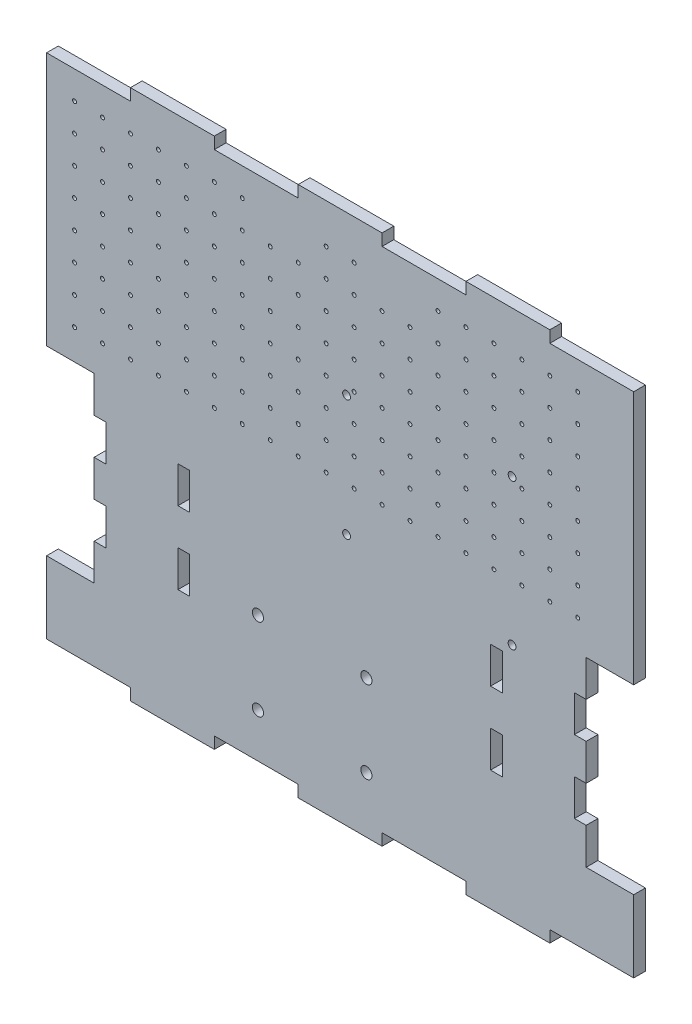
SolidWorks part; units mm, degrees
ref_plane "Front Plane" through (0, 0, 0) normal (0, 0, 1) x (1, 0, 0)
ref_plane "Top Plane" through (0, 0, 0) normal (0, 1, 0) x (1, 0, 0)
ref_plane "Right Plane" through (0, 0, 0) normal (1, 0, 0) x (0, 0, -1)
sketch "Sketch1" plane through (0, 0, 0) normal (0, 0, 1) x (1, 0, 0)
  line L1 (-133.35, 120.65) -> (133.35, 120.65)
  line L2 (-133.35, 120.65) -> (-133.35, -120.65)
  line L3 (-133.35, -120.65) -> (133.35, -120.65)
  line L4 (133.35, 120.65) -> (133.35, -120.65)
  line L5 (-133.35, 120.65) -> (133.35, -120.65) construction
  line L6 (-133.35, -120.65) -> (133.35, 120.65) construction
  point P0 (0, 0)
  dimension "D1" = 241.3
  dimension "D2" = 266.7
extrude "Boss-Extrude1" add sketch "Sketch1" along normal blind 5.334
sketch "Sketch2" plane through (0, 0, 0) normal (0, 0, -1) x (-1, 0, 0)
  line L0 (133.35, 120.65) -> (133.35, -120.65) construction
  line L1 (133.35, 0) -> (111.76, 0)
  line L2 (133.35, 0) -> (133.35, -82.55)
  line L3 (133.35, -82.55) -> (111.76, -82.55)
  line L4 (111.76, 0) -> (111.76, -82.55)
  line L5 (-133.35, -120.65) -> (-133.35, 120.65) construction
  line L6 (-133.35, 0) -> (-111.76, 0)
  line L7 (-133.35, 0) -> (-133.35, -82.55)
  line L8 (-133.35, -82.55) -> (-111.76, -82.55)
  line L9 (-111.76, 0) -> (-111.76, -82.55)
  line L10 (133.35, -120.65) -> (-133.35, -120.65) construction
  dimension "D1" = 82.55
  dimension "D2" = 82.55
  dimension "D3" = 38.1
  dimension "D4" = 38.1
  dimension "D5" = 21.59
  dimension "D6" = 21.59
extrude "Cut-Extrude1" cut sketch "Sketch2" against normal through all
sketch "Sketch9" plane through (0, 0, 5.334) normal (0, 0, 1) x (1, 0, 0)
  line L0 (-111.76, 0) -> (-111.76, -82.55) construction
  line L1 (-111.76, -16.51) -> (-106.426, -16.51)
  line L2 (-111.76, -16.51) -> (-111.76, -33.02)
  line L3 (-111.76, -33.02) -> (-106.426, -33.02)
  line L4 (-106.426, -16.51) -> (-106.426, -33.02)
  line L5 (-111.76, 0) -> (-106.426, 0) construction
  line L6 (-111.76, -49.53) -> (-106.426, -49.53)
  line L7 (-111.76, -49.53) -> (-111.76, -66.04)
  line L8 (-111.76, -66.04) -> (-106.426, -66.04)
  line L9 (-106.426, -49.53) -> (-106.426, -66.04)
  line L10 (-106.426, 0) -> (-106.426, -16.51) construction
  line L11 (-106.426, -33.02) -> (-106.426, -49.53) construction
  line L12 (-111.76, -82.55) -> (-106.426, -82.55) construction
  line L13 (-106.426, -82.55) -> (-106.426, -66.04) construction
  line L14 (0, -120.65) -> (0, 120.65) construction
  line L15 (-133.35, -120.65) -> (133.35, -120.65) construction
  line L16 (133.35, 120.65) -> (-133.35, 120.65) construction
  line L17 (106.426, -82.55) -> (106.426, -66.04) construction
  line L18 (111.76, -82.55) -> (106.426, -82.55) construction
  line L19 (106.426, -33.02) -> (106.426, -49.53) construction
  line L20 (106.426, 0) -> (106.426, -16.51) construction
  line L21 (111.76, 0) -> (106.426, 0) construction
  line L22 (106.426, -49.53) -> (106.426, -66.04)
  line L23 (111.76, -66.04) -> (106.426, -66.04)
  line L24 (111.76, -49.53) -> (111.76, -66.04)
  line L25 (111.76, -49.53) -> (106.426, -49.53)
  line L26 (106.426, -16.51) -> (106.426, -33.02)
  line L27 (111.76, -33.02) -> (106.426, -33.02)
  line L28 (111.76, -16.51) -> (111.76, -33.02)
  line L29 (111.76, -16.51) -> (106.426, -16.51)
  dimension "D1" = 5.334
extrude "Cut-Extrude2" cut sketch "Sketch9" against normal through all
sketch "Sketch10" plane through (0, 0, 5.334) normal (0, 0, 1) x (1, 0, 0)
  line L2 (-133.35, -120.65) -> (133.35, -120.65) construction
  line L3 (-133.35, -82.55) -> (-133.35, -120.65) construction
  circle A0 centre (-37.338, -95.25) radius 2.54
  circle A1 centre (11.938, -95.25) radius 2.54
  circle A2 centre (11.938, -57.912) radius 2.54
  circle A3 centre (-37.338, -57.912) radius 2.54
  dimension "D1" = 96.012
  dimension "D2" = 49.276
  dimension "D3" = 25.4
  dimension "D4" = 2
  dimension "D5" = 2
extrude "Cut-Extrude3" cut sketch "Sketch10" against normal through all
sketch "Sketch23" plane through (0, 0, 5.334) normal (0, 0, 1) x (1, 0, 0)
  line L0 (-106.426, -24.765) -> (-61.976, -24.765) construction
  line L1 (-106.426, -33.02) -> (-106.426, -16.51) construction
  line L2 (-106.426, -16.51) -> (-68.326, -16.51) construction
  line L3 (-106.426, -33.02) -> (-68.326, -33.02) construction
  line L4 (-111.76, -41.275) -> (111.76, -41.275) construction
  line L5 (-111.76, -33.02) -> (-111.76, -49.53) construction
  line L6 (111.76, -49.53) -> (111.76, -33.02) construction
  line L7 (-106.426, -49.53) -> (-68.326, -49.53) construction
  line L8 (-106.426, -57.785) -> (-61.976, -57.785) construction
  line L9 (-106.426, -66.04) -> (-68.326, -66.04) construction
  line L10 (0, -120.65) -> (0, 120.65) construction
  line L11 (-133.35, -120.65) -> (133.35, -120.65) construction
  line L12 (133.35, 120.65) -> (-133.35, 120.65) construction
  line L13 (106.426, -66.04) -> (68.326, -66.04) construction
  line L14 (106.426, -49.53) -> (68.326, -49.53) construction
  line L15 (106.426, -33.02) -> (68.326, -33.02) construction
  line L16 (106.426, -16.51) -> (68.326, -16.51) construction
  line L17 (-68.326, -66.04) -> (-73.66, -66.04)
  line L18 (68.326, -16.51) -> (73.66, -16.51)
  line L19 (68.326, -16.51) -> (68.326, -33.02)
  line L20 (68.326, -33.02) -> (73.66, -33.02)
  line L21 (73.66, -16.51) -> (73.66, -33.02)
  line L22 (68.326, -49.53) -> (73.66, -49.53)
  line L23 (68.326, -49.53) -> (68.326, -66.04)
  line L24 (68.326, -66.04) -> (73.66, -66.04)
  line L25 (73.66, -49.53) -> (73.66, -66.04)
  line L26 (-73.66, -49.53) -> (-73.66, -66.04)
  line L27 (-68.326, -49.53) -> (-68.326, -66.04)
  line L28 (-68.326, -49.53) -> (-73.66, -49.53)
  line L29 (-68.326, -33.02) -> (-73.66, -33.02)
  line L30 (-73.66, -16.51) -> (-73.66, -33.02)
  line L31 (-68.326, -16.51) -> (-73.66, -16.51)
  line L32 (-68.326, -16.51) -> (-68.326, -33.02)
  line L33 (106.426, -16.51) -> (106.426, -33.02) construction
  dimension "D1" = 5.334
  dimension "D2" = 5.334
  dimension "D3" = 32.766
  dimension "D4" = 32.766
extrude "Cut-Extrude8" cut sketch "Sketch23" against normal through all
sketch "Sketch28" plane through (0, 0, 0) normal (0, 0, -1) x (-1, 0, 0)
  line L0 (133.35, -120.65) -> (-133.35, -120.65) construction
  line L1 (-133.35, -120.65) -> (-95.25, -120.65)
  line L2 (-133.35, -120.65) -> (-133.35, -115.316)
  line L3 (-133.35, -115.316) -> (-95.25, -115.316)
  line L4 (-95.25, -120.65) -> (-95.25, -115.316)
  line L5 (-57.15, -120.65) -> (-19.05, -120.65)
  line L6 (-57.15, -120.65) -> (-57.15, -115.316)
  line L7 (-57.15, -115.316) -> (-19.05, -115.316)
  line L8 (-19.05, -120.65) -> (-19.05, -115.316)
  line L9 (133.35, -82.55) -> (133.35, -120.65) construction
  line L10 (19.05, -120.65) -> (57.15, -120.65)
  line L11 (19.05, -120.65) -> (19.05, -115.316)
  line L12 (19.05, -115.316) -> (57.15, -115.316)
  line L13 (57.15, -120.65) -> (57.15, -115.316)
  line L14 (95.25, -120.65) -> (133.35, -120.65)
  line L16 (95.25, -115.316) -> (133.35, -115.316)
  line L17 (133.35, -120.65) -> (133.35, -115.316)
  line L18 (-95.25, -115.316) -> (-57.15, -115.316) construction
  line L19 (-19.05, -115.316) -> (19.05, -115.316) construction
  line L20 (95.25, -115.316) -> (57.15, -115.316) construction
  line L21 (133.35, 120.65) -> (133.35, -115.316) construction
  line L22 (133.35, -115.316) -> (133.5431, -115.1744) construction
  line L41 (95.25, -120.65) -> (95.25, -115.316)
  dimension "D1" = 5.334
extrude "Cut-Extrude13" cut sketch "Sketch28" against normal through all
sketch "Sketch29" plane through (0, 0, 0) normal (0, 0, -1) x (-1, 0, 0)
  line L0 (-133.35, 120.65) -> (133.35, 120.65) construction
  line L1 (-133.35, 120.65) -> (-95.25, 120.65)
  line L2 (-133.35, 120.65) -> (-133.35, 115.316)
  line L3 (-133.35, 115.316) -> (-95.25, 115.316)
  line L4 (-95.25, 120.65) -> (-95.25, 115.316)
  line L5 (-57.15, 120.65) -> (-19.05, 120.65)
  line L6 (-57.15, 120.65) -> (-57.15, 115.316)
  line L7 (-57.15, 115.316) -> (-19.05, 115.316)
  line L8 (-19.05, 120.65) -> (-19.05, 115.316)
  line L9 (133.35, 120.65) -> (133.35, 0) construction
  line L10 (19.05, 120.65) -> (57.15, 120.65)
  line L11 (19.05, 120.65) -> (19.05, 115.316)
  line L12 (19.05, 115.316) -> (57.15, 115.316)
  line L13 (57.15, 120.65) -> (57.15, 115.316)
  line L14 (95.25, 120.65) -> (133.35, 120.65)
  line L15 (95.25, 120.65) -> (95.25, 115.316)
  line L16 (95.25, 115.316) -> (133.35, 115.316)
  line L17 (133.35, 120.65) -> (133.35, 115.316)
  line L18 (-95.25, 115.316) -> (-57.15, 115.316) construction
  line L19 (19.05, 115.316) -> (-19.05, 115.316) construction
  line L20 (57.15, 115.316) -> (95.25, 115.316) construction
  dimension "D1" = 5.334
extrude "Cut-Extrude14" cut sketch "Sketch29" against normal through all
sketch "Sketch30" plane through (0, 0, 5.334) normal (0, 0, 1) x (1, 0, 0)
  line L0 (-95.25, 115.316) -> (-133.35, 115.316) construction
  line L1 (-133.35, 115.316) -> (-133.35, 0) construction
  line L2 (-120.65, 102.616) -> (-107.95, 102.616) construction
  circle A0 centre (-120.65, 102.616) radius 0.889
  circle A1 centre (-107.95, 102.616) radius 0.889
  circle A2 centre (-95.25, 102.616) radius 0.889
  circle A3 centre (-82.55, 102.616) radius 0.889
  circle A4 centre (-69.85, 102.616) radius 0.889
  circle A5 centre (-57.15, 102.616) radius 0.889
  circle A6 centre (-44.45, 102.616) radius 0.889
  circle A7 centre (-31.75, 102.616) radius 0.889 [skipped]
  circle A8 centre (-19.05, 102.616) radius 0.889 [skipped]
  circle A9 centre (-6.35, 102.616) radius 0.889
  circle A10 centre (6.35, 102.616) radius 0.889
  circle A11 centre (19.05, 102.616) radius 0.889 [skipped]
  circle A12 centre (31.75, 102.616) radius 0.889 [skipped]
  circle A13 centre (44.45, 102.616) radius 0.889
  circle A14 centre (57.15, 102.616) radius 0.889
  circle A15 centre (69.85, 102.616) radius 0.889
  circle A16 centre (82.55, 102.616) radius 0.889
  circle A17 centre (95.25, 102.616) radius 0.889
  circle A18 centre (107.95, 102.616) radius 0.889
  circle A19 centre (-107.95, 89.916) radius 0.889
  circle A20 centre (-95.25, 89.916) radius 0.889
  circle A21 centre (-82.55, 89.916) radius 0.889
  circle A22 centre (-69.85, 89.916) radius 0.889
  circle A23 centre (-57.15, 89.916) radius 0.889
  circle A24 centre (-44.45, 89.916) radius 0.889
  circle A25 centre (-31.75, 89.916) radius 0.889
  circle A26 centre (-19.05, 89.916) radius 0.889
  circle A27 centre (-6.35, 89.916) radius 0.889
  circle A28 centre (6.35, 89.916) radius 0.889
  circle A29 centre (19.05, 89.916) radius 0.889
  circle A30 centre (31.75, 89.916) radius 0.889
  circle A31 centre (44.45, 89.916) radius 0.889
  circle A32 centre (57.15, 89.916) radius 0.889
  circle A33 centre (69.85, 89.916) radius 0.889
  circle A34 centre (82.55, 89.916) radius 0.889
  circle A35 centre (95.25, 89.916) radius 0.889
  circle A36 centre (107.95, 89.916) radius 0.889
  circle A37 centre (-107.95, 77.216) radius 0.889
  circle A38 centre (-95.25, 77.216) radius 0.889
  circle A39 centre (-82.55, 77.216) radius 0.889
  circle A40 centre (-69.85, 77.216) radius 0.889
  circle A41 centre (-57.15, 77.216) radius 0.889
  circle A42 centre (-44.45, 77.216) radius 0.889
  circle A43 centre (-31.75, 77.216) radius 0.889
  circle A44 centre (-19.05, 77.216) radius 0.889
  circle A45 centre (-6.35, 77.216) radius 0.889
  circle A46 centre (6.35, 77.216) radius 0.889
  circle A47 centre (19.05, 77.216) radius 0.889
  circle A48 centre (31.75, 77.216) radius 0.889
  circle A49 centre (44.45, 77.216) radius 0.889
  circle A50 centre (57.15, 77.216) radius 0.889
  circle A51 centre (69.85, 77.216) radius 0.889
  circle A52 centre (82.55, 77.216) radius 0.889
  circle A53 centre (95.25, 77.216) radius 0.889
  circle A54 centre (107.95, 77.216) radius 0.889
  circle A55 centre (-107.95, 64.516) radius 0.889
  circle A56 centre (-95.25, 64.516) radius 0.889
  circle A57 centre (-82.55, 64.516) radius 0.889
  circle A58 centre (-69.85, 64.516) radius 0.889
  circle A59 centre (-57.15, 64.516) radius 0.889
  circle A60 centre (-44.45, 64.516) radius 0.889
  circle A61 centre (-31.75, 64.516) radius 0.889
  circle A62 centre (-19.05, 64.516) radius 0.889
  circle A63 centre (-6.35, 64.516) radius 0.889
  circle A64 centre (6.35, 64.516) radius 0.889
  circle A65 centre (19.05, 64.516) radius 0.889
  circle A66 centre (31.75, 64.516) radius 0.889
  circle A67 centre (44.45, 64.516) radius 0.889
  circle A68 centre (57.15, 64.516) radius 0.889
  circle A69 centre (69.85, 64.516) radius 0.889
  circle A70 centre (82.55, 64.516) radius 0.889
  circle A71 centre (95.25, 64.516) radius 0.889
  circle A72 centre (107.95, 64.516) radius 0.889
  circle A73 centre (-107.95, 51.816) radius 0.889
  circle A74 centre (-95.25, 51.816) radius 0.889
  circle A75 centre (-82.55, 51.816) radius 0.889
  circle A76 centre (-69.85, 51.816) radius 0.889
  circle A77 centre (-57.15, 51.816) radius 0.889
  circle A78 centre (-44.45, 51.816) radius 0.889
  circle A79 centre (-31.75, 51.816) radius 0.889
  circle A80 centre (-19.05, 51.816) radius 0.889
  circle A81 centre (-6.35, 51.816) radius 0.889
  circle A82 centre (6.35, 51.816) radius 0.889
  circle A83 centre (19.05, 51.816) radius 0.889
  circle A84 centre (31.75, 51.816) radius 0.889
  circle A85 centre (44.45, 51.816) radius 0.889
  circle A86 centre (57.15, 51.816) radius 0.889
  circle A87 centre (69.85, 51.816) radius 0.889
  circle A88 centre (82.55, 51.816) radius 0.889
  circle A89 centre (95.25, 51.816) radius 0.889
  circle A90 centre (107.95, 51.816) radius 0.889
  circle A91 centre (-107.95, 39.116) radius 0.889
  circle A92 centre (-95.25, 39.116) radius 0.889
  circle A93 centre (-82.55, 39.116) radius 0.889
  circle A94 centre (-69.85, 39.116) radius 0.889
  circle A95 centre (-57.15, 39.116) radius 0.889
  circle A96 centre (-44.45, 39.116) radius 0.889
  circle A97 centre (-31.75, 39.116) radius 0.889
  circle A98 centre (-19.05, 39.116) radius 0.889
  circle A99 centre (-6.35, 39.116) radius 0.889
  circle A100 centre (6.35, 39.116) radius 0.889
  circle A101 centre (19.05, 39.116) radius 0.889
  circle A102 centre (31.75, 39.116) radius 0.889
  circle A103 centre (44.45, 39.116) radius 0.889
  circle A104 centre (57.15, 39.116) radius 0.889
  circle A105 centre (69.85, 39.116) radius 0.889
  circle A106 centre (82.55, 39.116) radius 0.889
  circle A107 centre (95.25, 39.116) radius 0.889
  circle A108 centre (107.95, 39.116) radius 0.889
  circle A109 centre (-107.95, 26.416) radius 0.889
  circle A110 centre (-95.25, 26.416) radius 0.889
  circle A111 centre (-82.55, 26.416) radius 0.889
  circle A112 centre (-69.85, 26.416) radius 0.889
  circle A113 centre (-57.15, 26.416) radius 0.889
  circle A114 centre (-44.45, 26.416) radius 0.889
  circle A115 centre (-31.75, 26.416) radius 0.889
  circle A116 centre (-19.05, 26.416) radius 0.889
  circle A117 centre (-6.35, 26.416) radius 0.889
  circle A118 centre (6.35, 26.416) radius 0.889
  circle A119 centre (19.05, 26.416) radius 0.889
  circle A120 centre (31.75, 26.416) radius 0.889
  circle A121 centre (44.45, 26.416) radius 0.889
  circle A122 centre (57.15, 26.416) radius 0.889
  circle A123 centre (69.85, 26.416) radius 0.889
  circle A124 centre (82.55, 26.416) radius 0.889
  circle A125 centre (95.25, 26.416) radius 0.889
  circle A126 centre (107.95, 26.416) radius 0.889
  circle A127 centre (-107.95, 13.716) radius 0.889
  circle A128 centre (-95.25, 13.716) radius 0.889
  circle A129 centre (-82.55, 13.716) radius 0.889
  circle A130 centre (-69.85, 13.716) radius 0.889
  circle A131 centre (-57.15, 13.716) radius 0.889
  circle A132 centre (-44.45, 13.716) radius 0.889
  circle A133 centre (-31.75, 13.716) radius 0.889
  circle A134 centre (-19.05, 13.716) radius 0.889
  circle A135 centre (-6.35, 13.716) radius 0.889
  circle A136 centre (6.35, 13.716) radius 0.889
  circle A137 centre (19.05, 13.716) radius 0.889
  circle A138 centre (31.75, 13.716) radius 0.889
  circle A139 centre (44.45, 13.716) radius 0.889
  circle A140 centre (57.15, 13.716) radius 0.889
  circle A141 centre (69.85, 13.716) radius 0.889
  circle A142 centre (82.55, 13.716) radius 0.889
  circle A143 centre (95.25, 13.716) radius 0.889
  circle A144 centre (107.95, 13.716) radius 0.889
  circle A145 centre (-120.65, 89.916) radius 0.889
  circle A146 centre (-120.65, 77.216) radius 0.889
  circle A147 centre (-120.65, 64.516) radius 0.889
  circle A148 centre (-120.65, 51.816) radius 0.889
  circle A149 centre (-120.65, 39.116) radius 0.889
  circle A150 centre (-120.65, 26.416) radius 0.889
  circle A151 centre (-120.65, 13.716) radius 0.889
  dimension "D1" = 1.778
  dimension "D2" = 12.7
  dimension "D3" = 12.7
  dimension "D6" = 12.7
  dimension "D4" = 19
  dimension "D5" = 8
extrude "Cut-Extrude15" cut sketch "Sketch30" against normal through all
sketch "Sketch32" plane through (0, 0, 0) normal (0, 0, -1) x (-1, 0, 0)
  circle A0 centre (-78.105, -11.938) radius 1.778 construction
  circle A1 centre (-2.921, -6.096) radius 1.778 construction
  circle A2 centre (-78.105, 54.356) radius 1.778 construction
  circle A3 centre (-2.921, 48.768) radius 1.778 construction
  circle A4 centre (-78.105, -11.938) radius 1.778
  circle A5 centre (-2.921, -6.096) radius 1.778
  circle A6 centre (-78.105, 54.356) radius 1.778
  circle A7 centre (-2.921, 48.768) radius 1.778
extrude "Cut-Extrude16" cut sketch "Sketch32" against normal through all
equation "\"MDF\"= .21in"
equation "\"Foamcore\"= .13in"
equation "\"Gmaterial\"= \"MDF\""
equation "\"D1@Sketch9\"=\"MDF\""
equation "\"D1@Sketch23\"=\"MDF\""
equation "\"D2@Sketch23\"=\"D1@Sketch23\""
equation "\"D1@Boss-Extrude1\"=\"MDF\""
equation "\"D3@Sketch23\"=1.29"
equation "\"D1@Sketch28\"=\"MDF\""
equation "\"D1@Sketch29\"=\"MDF\""
